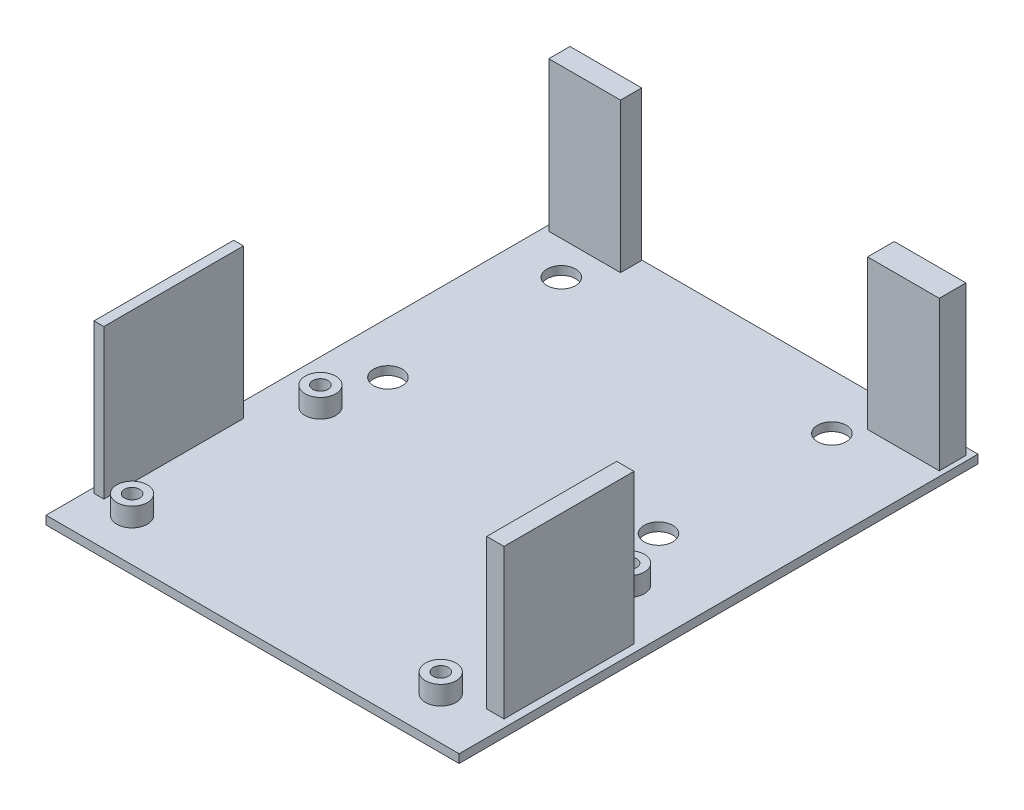
SolidWorks part; units mm, degrees
ref_plane "Front Plane" through (0, 0, 0) normal (0, 0, 1) x (1, 0, 0)
ref_plane "Top Plane" through (0, 0, 0) normal (0, 1, 0) x (1, 0, 0)
ref_plane "Right Plane" through (0, 0, 0) normal (1, 0, 0) x (0, 0, -1)
sketch "Sketch1" plane through (0, 0, 0) normal (0, 1, 0) x (1, 0, 0)
  line L1 (-45.4015, 82.3504) -> (40.9585, 82.3504)
  line L2 (-45.4015, 82.3504) -> (-45.4015, -26.1076)
  line L3 (-45.4015, -26.1076) -> (40.9585, -26.1076)
  line L4 (40.9585, 82.3504) -> (40.9585, -26.1076)
  line L5 (-44.2529, 82.262) -> (-29.2593, 82.262)
  line L6 (-44.2529, 82.262) -> (-44.2529, 77.8402)
  line L7 (-44.2529, 77.8402) -> (-29.2593, 77.8402)
  line L8 (-29.2593, 82.262) -> (-29.2593, 77.8402)
  line L9 (24.9445, 80.8515) -> (39.938, 80.8515)
  line L10 (24.9445, 80.8515) -> (24.9445, 75.2773)
  line L11 (24.9445, 75.2773) -> (39.938, 75.2773)
  line L12 (39.938, 80.8515) -> (39.938, 75.2773)
  line L13 (35.7414, 12.0392) -> (39.3614, 12.0392)
  line L14 (35.7414, 12.0392) -> (35.7414, -15.1274)
  line L15 (35.7414, -15.1274) -> (39.3614, -15.1274)
  line L16 (39.3614, 12.0392) -> (39.3614, -15.1274)
  line L17 (-44.3169, 12.0392) -> (-42.2666, 12.0392)
  line L18 (-44.3169, 12.0392) -> (-44.3169, -17.1505)
  line L19 (-44.3169, -17.1505) -> (-42.2666, -17.1505)
  line L20 (-42.2666, 12.0392) -> (-42.2666, -17.1505)
  circle A0 centre (-36.3626, 22.2195) radius 1.6
  circle A1 centre (28.1534, 22.2195) radius 1.6
  circle A2 centre (28.1534, -17.1505) radius 1.6
  circle A3 centre (-36.3626, -17.1505) radius 1.6
  circle A8 centre (-34.6101, 70.8225) radius 3
  circle A9 centre (21.943, 70.8225) radius 3
  circle A10 centre (-34.6101, 34.5767) radius 3
  circle A11 centre (21.943, 34.5767) radius 3
  circle A12 centre (-36.3626, 22.2195) radius 3.2
  circle A13 centre (28.1534, 22.2195) radius 3.2
  circle A14 centre (-36.3626, -17.1505) radius 3.2
  circle A15 centre (28.1534, -17.1505) radius 3.2
  dimension "D3" = 64.516
  dimension "D9" = 56.5531
  dimension "D1" = 86.36
  dimension "D2" = 108.458
  dimension "D4" = 64.516
  dimension "D7" = 39.37
  dimension "D8" = 39.37
  dimension "D10" = 56.5531
  dimension "D11" = 36.2458
  dimension "D12" = 36.2458
extrude "Boss-Extrude1" add sketch "Sketch1" along normal blind 1.778 contours L4 L1 L2 L3 A15 A14 A13 A12 A11 A10 A9 A8 region at (-2.375, 0, -27.8547)
extrude "Boss-Extrude2" add sketch "Sketch1<4>" along normal blind 5.715 contours A14 A3 | A15 A2 | A13 A1 | A12 A0 region at (-39.4721, 0, -22.2195) region at (25.0439, 0, -22.2195) region at (-39.4721, 0, 17.1505) region at (25.0439, 0, 17.1505)
sketch "Sketch1<4>" plane through (0, 0, 0) normal (0, 1, 0) x (1, 0, 0) same geometry as "Sketch1"
extrude "Boss-Extrude3" add sketch "Sketch1<5>" along normal blind 33.02 contours L8 L5 L6 L7 | L12 L9 L10 L11 | L16 L13 L14 L15 | L20 L17 L18 L19 region at (-36.7561, 0, -80.0511) region at (32.4412, 0, -78.0644) region at (37.5514, 0, 1.5441) region at (-43.2918, 0, 2.5556)
sketch "Sketch1<5>" plane through (0, 0, 0) normal (0, 1, 0) x (1, 0, 0) same geometry as "Sketch1"
